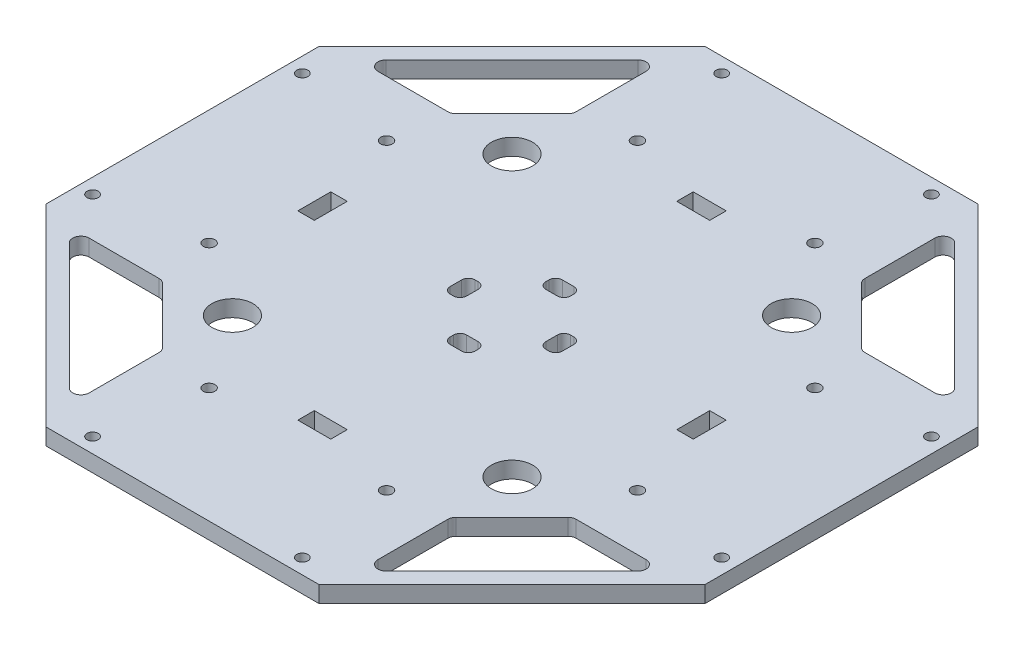
SolidWorks part; units mm, degrees
material "Custom Plastic"
ref_plane "Front Plane" through (0, 0, 0) normal (0, 0, 1) x (1, 0, 0)
ref_plane "Top Plane" through (0, 0, 0) normal (0, 1, 0) x (1, 0, 0)
ref_plane "Right Plane" through (0, 0, 0) normal (1, 0, 0) x (0, 0, -1)
ref_axis "Axis1" through (0, -0.2997, 0) along (0, 1, 0)
sketch "Base sketch" plane through (0, 0, 0) normal (0, 1, 0) x (1, 0, 0)
  line L1 (-127, 52.6051) -> (-127, -52.6051)
  line L2 (-127, -52.6051) -> (-52.6051, -127)
  line L3 (-52.6051, -127) -> (52.6051, -127)
  line L4 (52.6051, -127) -> (127, -52.6051)
  line L5 (127, -52.6051) -> (127, 52.6051)
  line L6 (127, 52.6051) -> (52.6051, 127)
  line L7 (52.6051, 127) -> (-52.6051, 127)
  line L8 (-52.6051, 127) -> (-127, 52.6051)
  circle A0 centre (0, 0) radius 127 construction
  dimension "D1" = 254
extrude "Base" add sketch "Base sketch" along normal blind 6.35
sketch "Sketch3" plane through (0, 6.35, 0) normal (0, 1, 0) x (1, 0, 0)
  line L0 (52.6051, 127) -> (-52.6051, 127) construction
  line L1 (-34.925, 114.3) -> (34.925, 114.3)
  line L2 (-34.925, 114.3) -> (-34.925, 79.375)
  line L4 (-34.925, 79.375) -> (34.925, 79.375)
  line L5 (34.925, 114.3) -> (34.925, 79.375)
  point P6 (0, 79.375)
  dimension "D1" = 69.85
  dimension "D2" = 34.925
  dimension "D3" = 12.7
sketch "Sketch4" plane through (0, 6.35, 0) normal (0, 1, 0) x (1, 0, 0)
  line L0 (0, 0) -> (0, 127) construction
  line L1 (52.6051, 127) -> (-52.6051, 127) construction
  line L4 (-6.35, 69.85) -> (6.35, 69.85)
  line L5 (-6.35, 69.85) -> (-6.35, 76.2)
  line L6 (-6.35, 76.2) -> (6.35, 76.2)
  line L7 (6.35, 69.85) -> (6.35, 76.2)
  line L8 (-6.35, 69.85) -> (6.35, 76.2) construction
  line L10 (-6.35, 76.2) -> (6.35, 69.85) construction
  point P5 (0, 73.025)
  dimension "D1" = 6.35
  dimension "D2" = 12.7
  dimension "D3" = 53.975
extrude "Support cutouts" cut sketch "Sketch4" against normal up to next
pattern_circular "Support cutout pattern" count 4 over 360 about axis through (0, -0.2997, 0) along (0, 1, 0) of "Support cutouts"
sketch "Sketch11" plane through (0, 6.35, 0) normal (0, 1, 0) x (1, 0, 0)
  line L1 (95.25, 39.4538) -> (39.4538, 95.25) construction
  line L2 (39.4538, 95.25) -> (-39.4538, 95.25) construction
  line L3 (-39.4538, 95.25) -> (-95.25, 39.4538) construction
  line L4 (-95.25, 39.4538) -> (-95.25, -39.4538) construction
  line L5 (-95.25, -39.4538) -> (-39.4538, -95.25) construction
  line L6 (-39.4538, -95.25) -> (39.4538, -95.25) construction
  line L7 (39.4538, -95.25) -> (95.25, -39.4538) construction
  line L8 (95.25, -39.4538) -> (95.25, 39.4538) construction
  line L9 (-34.1933, 82.55) -> (-82.55, 34.1933)
  line L10 (-82.55, 34.1933) -> (-82.55, -34.1933)
  line L11 (-82.55, -34.1933) -> (-34.1933, -82.55)
  line L12 (-34.1933, -82.55) -> (34.1933, -82.55)
  line L13 (34.1933, -82.55) -> (82.55, -34.1933)
  line L14 (82.55, -34.1933) -> (82.55, 34.1933)
  line L15 (82.55, 34.1933) -> (34.1933, 82.55)
  line L16 (34.1933, 82.55) -> (-34.1933, 82.55)
  circle A0 centre (0, 0) radius 95.25 construction
  circle A1 centre (0, 0) radius 82.55 construction
  dimension "D1" = 190.5
  dimension "D2" = 12.7
hole_wizard "#8 Clearance Hole1" positions "Sketch13" profile "Sketch12" hole size "#8" standard "ANSI Inch" end condition through all
sketch "Sketch13" plane through (0, 6.35, 0) normal (0, 1, 0) x (1, 0, 0)
  point P0 (-82.55, 34.1933)
  point P3 (-34.1933, 82.55)
  point P6 (34.1933, 82.55)
  point P9 (82.55, 34.1933)
  point P12 (82.55, -34.1933)
  point P15 (34.1933, -82.55)
  point P18 (-34.1933, -82.55)
  point P21 (-82.55, -34.1933)
sketch "Sketch12" plane through (-82.55, 6.35, -34.1933) normal (1, 0, 0) x (0, 0, 1)
  line L0 (0, 0) -> (0, 6.35)
  line L1 (0, 6.35) -> (2.2479, 6.35)
  line L2 (2.2479, 6.35) -> (2.2479, 0)
  line L5 (2.2479, 0) -> (0, 0)
  line L11 (0, -6.35) -> (0, 107.95) construction
  dimension "Thru Hole Dia." = 4.4958
  dimension "Thru Hole Depth" = 6.35
sketch "Sketch14" plane through (0, 6.35, 0) normal (0, 1, 0) x (1, 0, 0)
  circle A0 centre (-53.8815, 53.8815) radius 7.9375
  circle A1 centre (53.8815, 53.8815) radius 7.9375
  circle A2 centre (53.8815, -53.8815) radius 7.9375
  circle A3 centre (-53.8815, -53.8815) radius 7.9375
  point P13 (0, 0)
  dimension "D2" = 15.875
  dimension "D1" = 76.2
  dimension "D3" = 4
extrude "Cable holes" cut sketch "Sketch14" against normal up to next
sketch "Sketch18" plane through (0, 6.35, 0) normal (0, 1, 0) x (1, 0, 0)
  line L0 (89.8026, 89.8026) -> (0, 0) construction
  line L1 (127, 52.6051) -> (52.6051, 127) construction
  line L2 (40.4112, 121.2335) -> (121.2335, 40.4112) construction
  point P7 (80.8223, 80.8223)
  dimension "D1" = 114.3
  dimension "D2" = 12.7
hole_wizard "aligner mounting holes" positions "Sketch20" profile "Sketch19" hole size "#8" standard "ANSI Inch"
sketch "Sketch20" plane through (0, 6.35, 0) normal (0, 1, 0) x (1, 0, 0)
  point P0 (121.2335, 40.4112)
  point P7 (40.4112, 121.2335)
sketch "Sketch19" plane through (121.2335, 6.35, -40.4112) normal (1, 0, 0) x (0, 0, 1)
  line L0 (0, 0) -> (0, 6.351)
  line L1 (0, 6.351) -> (2.1526, 6.351)
  line L2 (2.1526, 6.351) -> (2.1526, 0)
  line L5 (2.1526, 0) -> (0, 0)
  line L10 (0, 6.351) -> (-2.1527, 6.351) construction
  line L11 (0, -6.35) -> (0, 107.95) construction
  dimension "Hole Dia." = 4.3053
  dimension "Hole Depth" = 6.351
  dimension "Drill Angle" = 180
pattern_circular "CirPattern1" count 4 over 360 about axis through (0, -0.2997, 0) along (0, 1, 0) of "aligner mounting holes"
sketch "Sketch28" plane through (0, 6.35, 0) normal (0, 1, 0) x (1, 0, 0)
  line L0 (52.6051, 127) -> (-52.6051, 127) construction
  line L1 (55.6512, 80.3678) -> (55.6512, 107.3086)
  line L2 (61.0712, 109.5536) -> (109.5536, 61.0712)
  line L3 (78.1228, 56.5811) -> (56.5811, 78.1228)
  line L4 (-127, 52.6051) -> (-127, -52.6051) construction
  line L5 (107.3086, 55.6512) -> (80.3678, 55.6512)
  line L6 (80.3678, -55.6512) -> (107.3086, -55.6512)
  line L7 (109.5536, -61.0712) -> (61.0712, -109.5536)
  line L8 (56.5811, -78.1228) -> (78.1228, -56.5811)
  line L9 (55.6512, -107.3086) -> (55.6512, -80.3678)
  line L10 (-55.6512, -80.3678) -> (-55.6512, -107.3086)
  line L11 (-61.0712, -109.5536) -> (-109.5536, -61.0712)
  line L12 (-56.5811, 78.1228) -> (-78.1228, 56.5811)
  line L13 (-55.6512, 107.3086) -> (-55.6512, 80.3678)
  line L14 (-109.5536, 61.0712) -> (-61.0712, 109.5536)
  line L15 (-80.3678, 55.6512) -> (-107.3086, 55.6512)
  line L16 (-78.1228, -56.5811) -> (-56.5811, -78.1228)
  line L17 (-107.3086, -55.6512) -> (-80.3678, -55.6512)
  line L20 (0, 0) -> (-89.8026, 89.8026) construction
  line L21 (-52.6051, 127) -> (-127, 52.6051) construction
  circle A0 centre (-40.4112, 121.2335) radius 2.1527 construction
  arc A1 (61.0712, 109.5536) -> (55.6512, 107.3086) centre (58.8262, 107.3086) ccw
  arc A2 (55.6512, 80.3678) -> (56.5811, 78.1228) centre (58.8262, 80.3678) ccw
  arc A3 (78.1228, 56.5811) -> (80.3678, 55.6512) centre (80.3678, 58.8262) ccw
  circle A4 centre (-34.1933, 82.55) radius 2.2479 construction
  arc A5 (107.3086, 55.6512) -> (109.5536, 61.0712) centre (107.3086, 58.8262) ccw
  arc A6 (109.5536, -61.0712) -> (107.3086, -55.6512) centre (107.3086, -58.8262) ccw
  arc A7 (80.3678, -55.6512) -> (78.1228, -56.5811) centre (80.3678, -58.8262) ccw
  arc A8 (56.5811, -78.1228) -> (55.6512, -80.3678) centre (58.8262, -80.3678) ccw
  arc A9 (55.6512, -107.3086) -> (61.0712, -109.5536) centre (58.8262, -107.3086) ccw
  arc A10 (-61.0712, -109.5536) -> (-55.6512, -107.3086) centre (-58.8262, -107.3086) ccw
  arc A11 (-55.6512, -80.3678) -> (-56.5811, -78.1228) centre (-58.8262, -80.3678) ccw
  arc A12 (-80.3678, 55.6512) -> (-78.1228, 56.5811) centre (-80.3678, 58.8262) ccw
  arc A13 (-56.5811, 78.1228) -> (-55.6512, 80.3678) centre (-58.8262, 80.3678) ccw
  arc A14 (-55.6512, 107.3086) -> (-61.0712, 109.5536) centre (-58.8262, 107.3086) ccw
  arc A15 (-109.5536, 61.0712) -> (-107.3086, 55.6512) centre (-107.3086, 58.8262) ccw
  arc A16 (-78.1228, -56.5811) -> (-80.3678, -55.6512) centre (-80.3678, -58.8262) ccw
  arc A17 (-107.3086, -55.6512) -> (-109.5536, -61.0712) centre (-107.3086, -58.8262) ccw
  point P51 (0, 0)
  point P54 (-85.3124, 85.3124)
  point P55 (-67.3519, 67.3519)
  point P67 (0, 0)
  dimension "D3" = 3.175
  dimension "D4" = 15.24
  dimension "D1" = 6.35
  dimension "D2" = 31.75
  dimension "D5" = 4
extrude "Cut-Extrude2" cut sketch "Sketch28" against normal through all
sketch "Sketch29" plane through (0, 6.35, 0) normal (0, 1, 0) x (1, 0, 0)
  line L0 (18.415, 0) -> (0, 0) construction
  line L1 (15.24, -2.2225) -> (15.24, 2.2225)
  line L2 (17.78, -4.7625) -> (19.05, -4.7625)
  line L3 (0, 18.415) -> (0, 0) construction
  line L4 (15.24, -4.7625) -> (21.59, 4.7625) construction
  line L5 (2.2225, 15.24) -> (-2.2225, 15.24)
  line L6 (4.7625, 17.78) -> (4.7625, 19.05)
  line L7 (2.2225, 21.59) -> (-2.2225, 21.59)
  line L8 (-4.7625, 17.78) -> (-4.7625, 19.05)
  line L9 (4.7625, 15.24) -> (-4.7625, 21.59) construction
  line L10 (4.7625, 21.59) -> (-4.7625, 15.24) construction
  line L11 (21.59, -4.7625) -> (15.24, 4.7625) construction
  line L12 (17.78, 4.7625) -> (19.05, 4.7625)
  line L13 (21.59, -2.2225) -> (21.59, 2.2225)
  line L14 (0, -18.415) -> (0, 0) construction
  line L15 (-2.2225, -15.24) -> (2.2225, -15.24)
  line L16 (-4.7625, -17.78) -> (-4.7625, -19.05)
  line L17 (-4.7625, -15.24) -> (4.7625, -21.59) construction
  line L18 (-4.7625, -21.59) -> (4.7625, -15.24) construction
  line L19 (4.7625, -17.78) -> (4.7625, -19.05)
  line L20 (-2.2225, -21.59) -> (2.2225, -21.59)
  line L21 (-18.415, 0) -> (0, 0) construction
  line L22 (-15.24, 2.2225) -> (-15.24, -2.2225)
  line L23 (-17.78, 4.7625) -> (-19.05, 4.7625)
  line L24 (-15.24, 4.7625) -> (-21.59, -4.7625) construction
  line L25 (-21.59, 4.7625) -> (-15.24, -4.7625) construction
  line L26 (-17.78, -4.7625) -> (-19.05, -4.7625)
  line L27 (-21.59, 2.2225) -> (-21.59, -2.2225)
  arc A0 (-2.2225, 21.59) -> (-4.7625, 19.05) centre (-2.2225, 19.05) ccw
  arc A1 (-2.2225, 15.24) -> (-4.7625, 17.78) centre (-2.2225, 17.78) cw
  arc A2 (2.2225, 15.24) -> (4.7625, 17.78) centre (2.2225, 17.78) ccw
  arc A3 (4.7625, 19.05) -> (2.2225, 21.59) centre (2.2225, 19.05) ccw
  arc A4 (15.24, -2.2225) -> (17.78, -4.7625) centre (17.78, -2.2225) ccw
  arc A5 (15.24, 2.2225) -> (17.78, 4.7625) centre (17.78, 2.2225) cw
  arc A6 (21.59, 2.2225) -> (19.05, 4.7625) centre (19.05, 2.2225) ccw
  arc A7 (19.05, -4.7625) -> (21.59, -2.2225) centre (19.05, -2.2225) ccw
  arc A8 (-2.2225, -15.24) -> (-4.7625, -17.78) centre (-2.2225, -17.78) ccw
  arc A9 (2.2225, -15.24) -> (4.7625, -17.78) centre (2.2225, -17.78) cw
  arc A10 (2.2225, -21.59) -> (4.7625, -19.05) centre (2.2225, -19.05) ccw
  arc A11 (-4.7625, -19.05) -> (-2.2225, -21.59) centre (-2.2225, -19.05) ccw
  arc A12 (-15.24, 2.2225) -> (-17.78, 4.7625) centre (-17.78, 2.2225) ccw
  arc A13 (-15.24, -2.2225) -> (-17.78, -4.7625) centre (-17.78, -2.2225) cw
  arc A14 (-21.59, -2.2225) -> (-19.05, -4.7625) centre (-19.05, -2.2225) ccw
  arc A15 (-19.05, 4.7625) -> (-21.59, 2.2225) centre (-19.05, 2.2225) ccw
  point P73 (0, 0)
  dimension "D4" = 2.54
  dimension "D1" = 18.415
  dimension "D2" = 6.35
  dimension "D3" = 9.525
extrude "Cut-Extrude3" cut sketch "Sketch29" against normal through all
equation "\"MAT_THICKNESS\"=0.25"
equation "\"D1@Base\"=\"MAT_THICKNESS\""
equation "\"D1@Sketch4\"=\"MAT_THICKNESS\""
